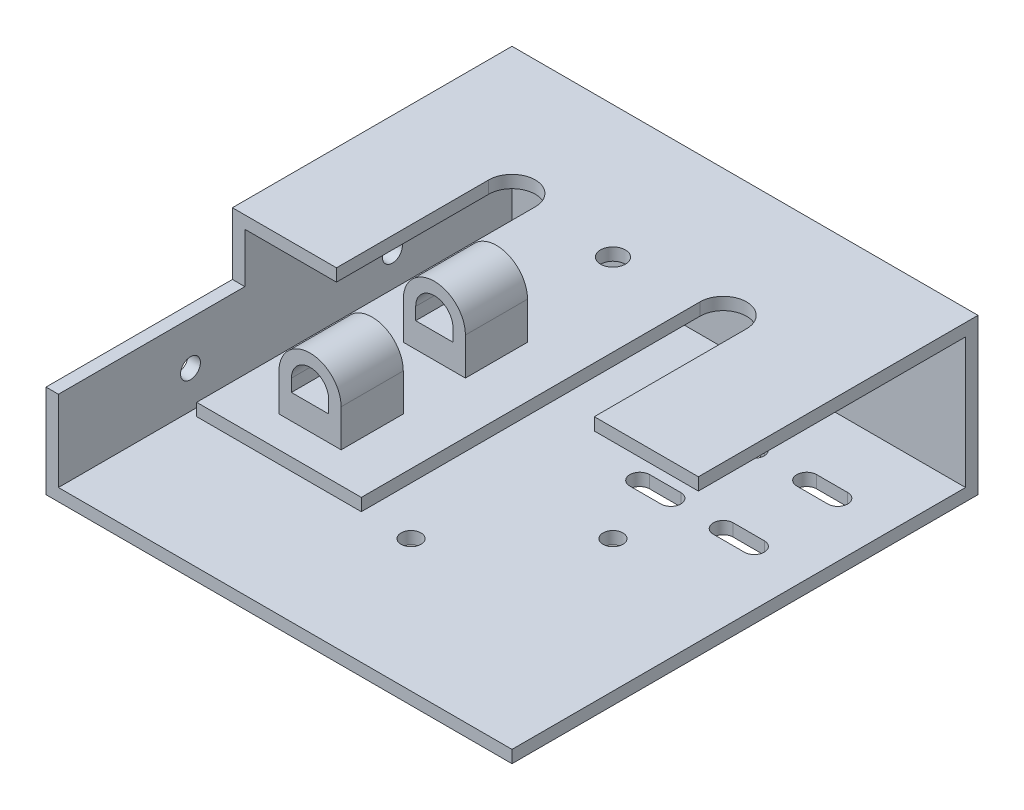
SolidWorks part; units mm, degrees
ref_plane "Front Plane" through (0, 0, 0) normal (0, 0, 1) x (1, 0, 0)
ref_plane "Top Plane" through (0, 0, 0) normal (0, 1, 0) x (1, 0, 0)
ref_plane "Right Plane" through (0, 0, 0) normal (1, 0, 0) x (0, 0, -1)
sketch "Sketch2" plane through (0, 0, 0) normal (0, 1, 0) x (1, 0, 0)
  line L1 (-37.5, 37.5) -> (37.5, 37.5)
  line L2 (-37.5, 37.5) -> (-37.5, -37.5)
  line L3 (-37.5, -37.5) -> (37.5, -37.5)
  line L4 (37.5, 37.5) -> (37.5, -37.5)
  line L5 (-37.5, 37.5) -> (37.5, -37.5) construction
  line L6 (-37.5, -37.5) -> (37.5, 37.5) construction
  point P0 (0, 0)
  dimension "D1" = 75
  dimension "D2" = 75
extrude "Boss-Extrude1" add sketch "Sketch2" along normal blind 25
shell "Shell1" thickness 2 removed face at (0, 12.5, 37.5) removed face at (37.5, 12.5, 0)
sketch "Sketch3" plane through (0, 2, 0) normal (0, 1, 0) x (1, 0, 0)
  line L0 (0, 0) -> (0, 17) construction
  line L1 (-23.7175, 23.7175) -> (-10.2825, 23.7175) construction
  line L2 (-23.7175, 23.7175) -> (-23.7175, 10.2825) construction
  line L3 (-23.7175, 10.2825) -> (-10.2825, 10.2825) construction
  line L4 (-10.2825, 23.7175) -> (-10.2825, 10.2825) construction
  line L5 (-23.7175, 23.7175) -> (-10.2825, 10.2825) construction
  line L6 (-23.7175, 10.2825) -> (-10.2825, 23.7175) construction
  line L7 (10.2825, 23.7175) -> (23.7175, 23.7175) construction
  line L8 (10.2825, 23.7175) -> (10.2825, 10.2825) construction
  line L9 (10.2825, 10.2825) -> (23.7175, 10.2825) construction
  line L10 (23.7175, 23.7175) -> (23.7175, 10.2825) construction
  line L11 (10.2825, 23.7175) -> (23.7175, 10.2825) construction
  line L12 (10.2825, 10.2825) -> (23.7175, 23.7175) construction
  line L13 (37.5, -37.5) -> (37.5, 37.5) construction
  line L14 (37.5, 37.5) -> (-37.5, 37.5) construction
  circle A0 centre (-23.7175, 23.7175) radius 1.6
  circle A1 centre (-10.2825, 23.7175) radius 1.6
  circle A2 centre (-10.2825, 10.2825) radius 1.6
  circle A3 centre (-23.7175, 10.2825) radius 1.6
  circle A4 centre (10.2825, 23.7175) radius 1.6
  circle A5 centre (23.7175, 23.7175) radius 1.6
  circle A6 centre (10.2825, 10.2825) radius 1.6
  circle A7 centre (23.7175, 10.2825) radius 1.6
  circle A8 centre (17, 17) radius 17 construction
  point P0 (-17, 17)
  point P5 (17, 17)
  dimension "D2" = 3.2
  dimension "D5" = 34
  dimension "D1" = 19
  dimension "D3" = 17
  dimension "D4" = 17
  dimension "D6" = 20.5
  dimension "D7" = 20.5
extrude "Cut-Extrude1" cut sketch "Sketch3" against normal blind 50
sketch "Sketch4" plane through (0, 25, 0) normal (0, 1, 0) x (1, 0, 0)
  line L0 (-23.7175, 10.2825) -> (-10.2825, 23.7175) construction
  line L1 (37.5, -37.5) -> (37.5, 37.5) construction
  line L2 (-37.5, -37.5) -> (-13.25, -37.5)
  line L3 (-37.5, -37.5) -> (-37.5, -7.5)
  line L4 (-37.5, -7.5) -> (-20.75, -7.5)
  line L5 (37.5, -37.5) -> (37.5, -7.5)
  line L6 (-20.75, 17) -> (-20.75, -7.5)
  line L8 (-13.25, 17) -> (-13.25, -7.5)
  line L9 (20.75, -7.5) -> (37.5, -7.5)
  line L10 (13.25, 17) -> (13.25, -7.5)
  line L11 (-13.25, -7.5) -> (-13.25, -37.5)
  line L12 (20.75, 17) -> (20.75, -7.5)
  line L13 (13.25, -37.5) -> (37.5, -37.5)
  line L14 (13.25, -7.5) -> (13.25, -37.5)
  arc A0 (20.75, 17) -> (13.25, 17) centre (17, 17) ccw
  arc A1 (-13.25, 17) -> (-20.75, 17) centre (-17, 17) ccw
  point P22 (37.5, -6.61)
  dimension "D1" = 7.5
  dimension "D2" = 30
extrude "Cut-Extrude2" cut sketch "Sketch4" against normal blind 10
sketch "Sketch5" plane through (0, 0, 37.5) normal (0, 0, 1) x (1, 0, 0)
  line L0 (-5, 25) -> (-5, 31)
  line L1 (-13.25, 25) -> (13.25, 25) construction
  line L3 (5, 31) -> (5, 25)
  line L4 (5, 25) -> (-5, 25)
  line L8 (3, 27) -> (-3, 27) construction
  line L9 (-3, 27) -> (-3, 31) construction
  line L10 (3, 31) -> (3, 27) construction
  line L11 (-3, 31) -> (-3, 29)
  line L12 (-3, 29) -> (3, 29)
  line L13 (3, 29) -> (3, 31)
  arc A0 (-5, 31) -> (5, 31) centre (0, 31) cw
  arc A1 (-3, 31) -> (3, 31) centre (0, 31) cw
  dimension "D2" = 10
  dimension "D1" = 6
  dimension "D4" = 2
  dimension "D3" = 2
extrude "Boss-Extrude2" add sketch "Sketch5" against normal blind 10 from offset 5 offset against normal yes
sketch "Sketch6" plane through (0, 25, 0) normal (0, 1, 0) x (1, 0, 0)
  line L0 (-2.1822, -22.5) -> (0, -27.5)
  line L1 (-5, -22.5) -> (5, -22.5) construction
  line L2 (0, -27.5) -> (-2.1822, -32.5)
  line L3 (-5, -32.5) -> (5, -32.5) construction
  line L4 (-2.1822, -22.5) -> (0, -22.5)
  line L5 (0, -22.5) -> (2.1822, -27.5)
  line L6 (2.1822, -27.5) -> (0, -32.5)
  line L7 (-5, -32.5) -> (5, -32.5) construction
  line L8 (0, -32.5) -> (-2.1822, -32.5)
  line L13 (-5, -32.5) -> (5, -32.5)
  line L14 (5, -32.5) -> (5, -22.5)
  line L15 (5, -22.5) -> (-5, -22.5)
  line L16 (-5, -22.5) -> (-5, -32.5)
  line L17 (-5, -32.5) -> (5, -32.5) construction
  line L18 (5, -32.5) -> (5, -22.5) construction
  line L19 (5, -22.5) -> (-5, -22.5) construction
  line L20 (-5, -22.5) -> (-5, -32.5) construction
  point P14 (-5, -27.5)
  point P16 (0, -32.5)
  point P18 (2.3234, -17.5)
  point P19 (0, -22.5)
  dimension "D2" = 2
  dimension "D1" = 0
extrude "Cut-Extrude3" [suppressed] cut sketch "Sketch6" along normal through all from offset 5
pattern_linear "LPattern1" count 2 spacing 20 along (0, 0, -1) of "Boss-Extrude2", "Cut-Extrude3"
fillet "Fillet2" [suppressed] radius 2
sketch "Sketch7" plane through (0, 0, 0) normal (0, -1, 0) x (1, 0, 0)
  line L1 (0, 16.25) -> (16.25, 0) construction
  line L2 (0, 16.25) -> (-16.25, 0) construction
  line L3 (-16.25, 0) -> (0, -16.25) construction
  line L4 (16.25, 0) -> (0, -16.25) construction
  line L5 (0, 16.25) -> (0, -16.25) construction
  line L6 (-16.25, 0) -> (16.25, 0) construction
  circle A0 centre (0, 16.25) radius 1.6
  circle A1 centre (16.25, 0) radius 1.6
  circle A2 centre (0, -16.25) radius 1.6
  circle A3 centre (-16.25, 0) radius 1.6
  point P0 (0, 0)
  point P9 (0, 11.6597)
  point P11 (0, 7.9761)
  point P12 (0, 3.7798)
  point P13 (0, 0)
  dimension "D2" = 3.2
  dimension "D1" = 32.5
  dimension "D4" = 32.5
extrude "Cut-Extrude4" cut sketch "Sketch7" against normal blind 10
sketch "Sketch9" plane through (-35.5, 0, 0) normal (1, 0, 0) x (0, 0, -1)
  line L0 (-16.25, 8) -> (16.25, 8) construction
  line L1 (35.5, 2) -> (-37.5, 2) construction
  circle A0 centre (-16.25, 8) radius 1.6
  circle A1 centre (16.25, 8) radius 1.6
  point P3 (0, 8)
  point P6 (0, 7.1874)
  dimension "D1" = 3.2
  dimension "D2" = 32.5
  dimension "D3" = 6
extrude "Cut-Extrude5" cut sketch "Sketch9" against normal blind 10
sketch "Sketch10" plane through (0, 25, 0) normal (0, 1, 0) x (1, 0, 0)
  circle A1 centre (0, 16.25) radius 2
  point P1 (0, 0)
  dimension "D1" = 4
extrude "Cut-Extrude6" cut sketch "Sketch10" against normal blind 10
sketch "Sketch11" plane through (0, 0, 0) normal (0, -1, 0) x (1, 0, 0)
  line L0 (10.2825, -10.2825) -> (15.2825, -10.2825) construction
  line L1 (10.2825, -8.6825) -> (15.2825, -8.6825)
  line L2 (10.2825, -11.8825) -> (15.2825, -11.8825)
  line L3 (23.7175, -10.2825) -> (28.7175, -10.2825) construction
  line L4 (23.7175, -8.6825) -> (28.7175, -8.6825)
  line L5 (23.7175, -11.8825) -> (28.7175, -11.8825)
  line L6 (23.7175, -23.7175) -> (28.7175, -23.7175) construction
  line L7 (23.7175, -22.1175) -> (28.7175, -22.1175)
  line L8 (23.7175, -25.3175) -> (28.7175, -25.3175)
  line L9 (10.2825, -23.7175) -> (15.2825, -23.7175) construction
  line L10 (10.2825, -22.1175) -> (15.2825, -22.1175)
  line L11 (10.2825, -25.3175) -> (15.2825, -25.3175)
  arc A0 (10.2825, -8.6825) -> (10.2825, -11.8825) centre (10.2825, -10.2825) ccw
  arc A1 (15.2825, -11.8825) -> (15.2825, -8.6825) centre (15.2825, -10.2825) ccw
  arc A2 (23.7175, -8.6825) -> (23.7175, -11.8825) centre (23.7175, -10.2825) ccw
  arc A3 (28.7175, -11.8825) -> (28.7175, -8.6825) centre (28.7175, -10.2825) ccw
  arc A4 (23.7175, -22.1175) -> (23.7175, -25.3175) centre (23.7175, -23.7175) ccw
  arc A5 (28.7175, -25.3175) -> (28.7175, -22.1175) centre (28.7175, -23.7175) ccw
  arc A6 (10.2825, -22.1175) -> (10.2825, -25.3175) centre (10.2825, -23.7175) ccw
  arc A7 (15.2825, -25.3175) -> (15.2825, -22.1175) centre (15.2825, -23.7175) ccw
  circle A8 centre (23.7175, -23.7175) radius 1.6 construction
  point P3 (12.7825, -10.2825)
  point P8 (26.2175, -10.2825)
  point P16 (26.2175, -23.7175)
  point P24 (12.7825, -23.7175)
  dimension "D1" = 5
extrude "Cut-Extrude7" cut sketch "Sketch11" against normal blind 10
equation "\"D4@Sketch3\"=\"D3@Sketch3\""
